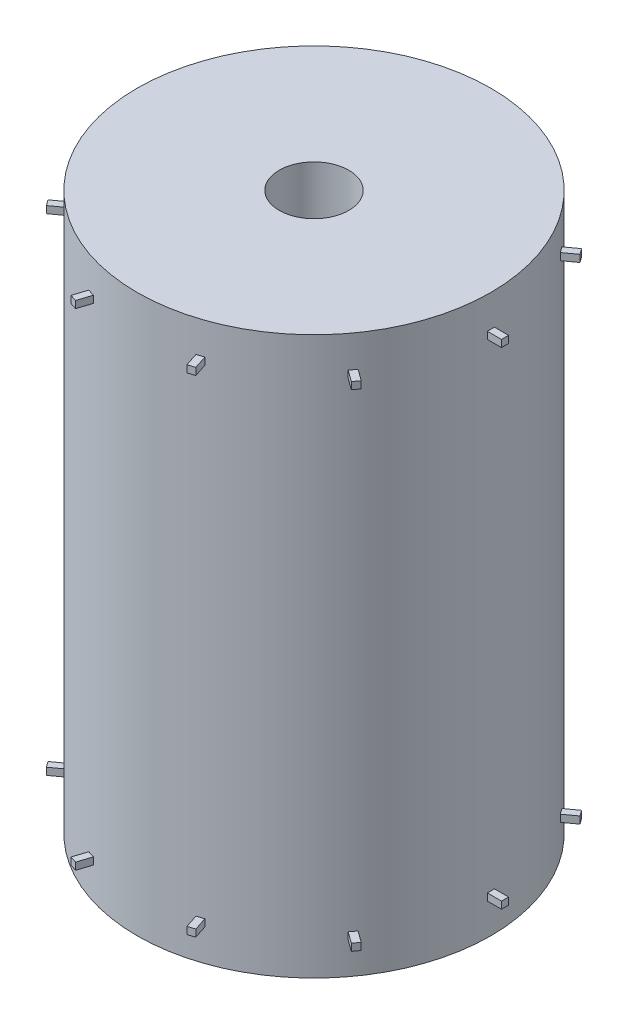
SolidWorks part; units mm, degrees
ref_plane "Front Plane" through (0, 0, 0) normal (0, 0, 1) x (1, 0, 0)
ref_plane "Top Plane" through (0, 0, 0) normal (0, 1, 0) x (1, 0, 0)
ref_plane "Right Plane" through (0, 0, 0) normal (1, 0, 0) x (0, 0, -1)
sketch "Sketch1" plane through (0, 0, 0) normal (0, 1, 0) x (1, 0, 0)
  circle A0 centre (0, 0) radius 12.7
  dimension "D1" = 25.4
extrude "Boss-Extrude1" add sketch "Sketch1" along normal blind 40
hole_wizard "Ø5.0mm Dowel Hole1" positions "Sketch5" profile "Sketch6" hole size "Ø5.0" standard "ANSI Metric" end condition through all
sketch "Sketch5" plane through (0, 40, 0) normal (0, 1, 0) x (1, 0, 0)
  point P0 (0, 0)
sketch "Sketch6" plane through (0, 40, 0) normal (1, 0, 0) x (0, 0, 1)
  line L0 (0, 0) -> (0, 40)
  line L1 (0, 40) -> (2.5, 40)
  line L2 (2.5, 40) -> (2.5, 0)
  line L5 (2.5, 0) -> (0, 0)
  line L11 (0, -6.35) -> (0, 107.95) construction
  dimension "Thru Hole Dia." = 5
  dimension "Thru Hole Depth" = 40
sketch "Sketch4" plane through (0, 40, 0) normal (0, 1, 0) x (1, 0, 0)
  line L1 (12.6975, 0.254) -> (13.7135, 0.254)
  line L2 (12.6975, 0.254) -> (12.6975, -0.254)
  line L3 (12.6975, -0.254) -> (13.7135, -0.254)
  line L4 (13.7135, 0.254) -> (13.7135, -0.254)
  circle A1 centre (0, 0) radius 12.7
  circle A2 centre (0, 0) radius 12.7
  circle M12 centre (0, 0) radius 12.7
  dimension "D2" = 0.508
  dimension "D3" = 1.016
extrude "Boss-Extrude2" add sketch "Sketch4" along normal blind 0.508 from offset 2.794 contours L4 L1 L3 M12 region at (13.2063, 40, 0) offset against normal yes
ref_plane "Plane1" through (0, 20, 0) normal (0, 1, 0) x (1, 0, 0)
mirror "Mirror4" about plane through (0, 20, 0) normal (0, 1, 0) of "Boss-Extrude2"
pattern_circular "CirPattern3" count 10 over 360 about axis through (0, 0, 0) along (0, 1, 0) of "Boss-Extrude2", "Mirror4"
equation "\"diamiter\" = 1"
equation "\"D1@Sketch1\"=\"diamiter\""
equation "\"tooth width\"= 0.5mm"
equation "\"Tooth Depth\"= 1mm"
equation "\"D2@Sketch4\"=\"tooth width\""
equation "\"D3@Sketch4\"=\"Tooth Depth\""
equation "\"Tooth height\"= 0.5mm"
equation "\"tooth offset\"= 2.5mm"
equation "\"D1@Boss-Extrude2\"=\"Tooth height\""
equation "\"D19@Boss-Extrude2\"=\"tooth offset\"+\"Tooth height\"/2"
equation "\"Number of teeth\"= 10"
equation "\"D1@CirPattern1\"=\"Number of teeth\""
